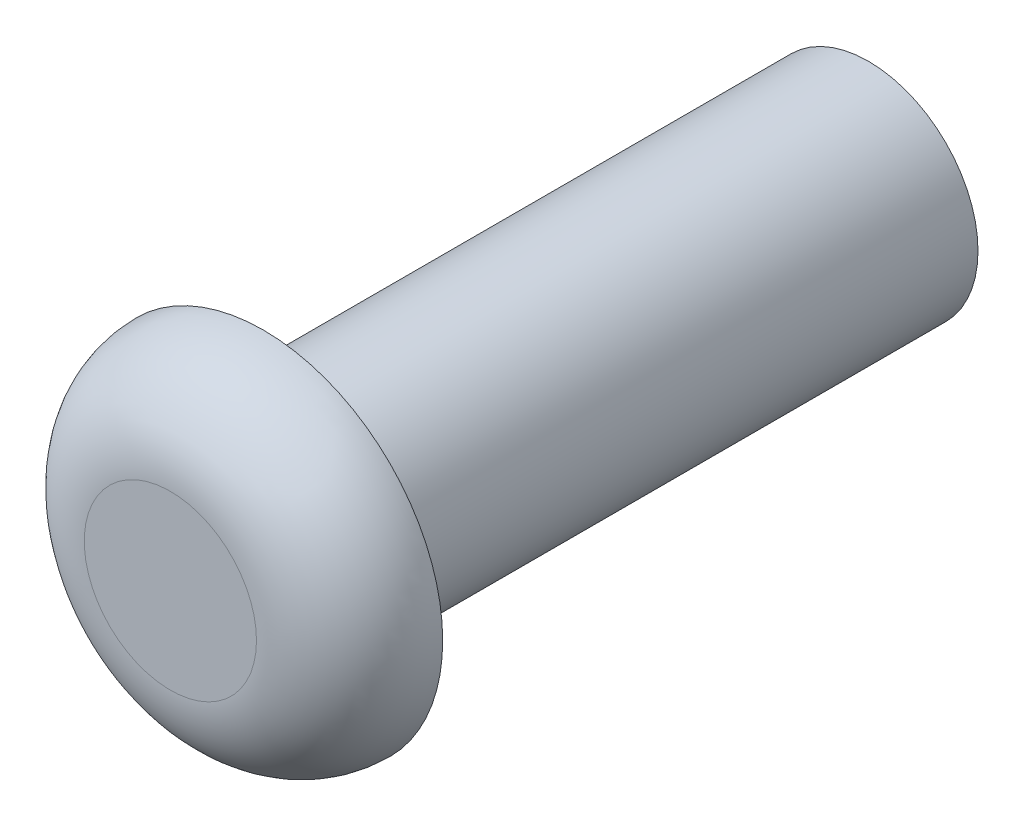
SolidWorks part; units mm, degrees
ref_plane "Płaszczyzna przednia" through (0, 0, 0) normal (0, 0, 1) x (1, 0, 0)
ref_plane "Płaszczyzna górna" through (0, 0, 0) normal (0, 1, 0) x (1, 0, 0)
ref_plane "Płaszczyzna prawa" through (0, 0, 0) normal (1, 0, 0) x (0, 0, -1)
sketch "Szkic1" plane through (0, 0, 0) normal (0, 0, 1) x (1, 0, 0)
  circle A0 centre (0, 0) radius 2.35
  dimension "D1" = 4.7
extrude "Dodanie-wyciągnięcie1" add sketch "Szkic1" along normal blind 13
sketch "Szkic3" plane through (0, 0, 13) normal (0, 0, 1) x (1, 0, 0)
  circle A0 centre (0, 0) radius 3.85
  dimension "D1" = 7.7
extrude "Dodanie-wyciągnięcie2" add sketch "Szkic3" along normal blind 2
fillet "Zaokrąglenie1" radius 2 1 edges at (3.85, 0, 15)
